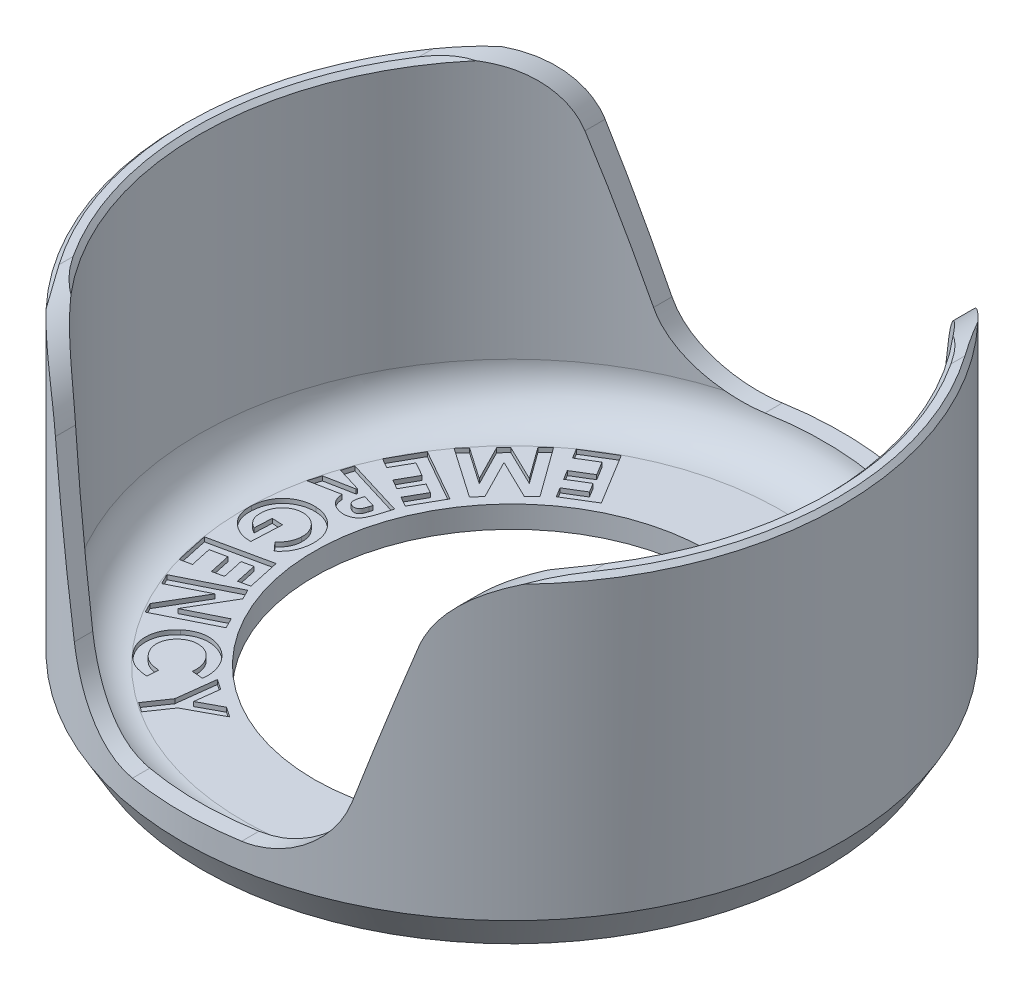
SolidWorks part; units mm, degrees
ref_plane "Front Plane" through (0, 0, 0) normal (0, 0, 1) x (1, 0, 0)
ref_plane "Top Plane" through (0, 0, 0) normal (0, 1, 0) x (1, 0, 0)
ref_plane "Right Plane" through (0, 0, 0) normal (1, 0, 0) x (0, 0, -1)
sketch "Sketch1" plane through (0, 0, 0) normal (0, 1, 0) x (1, 0, 0)
  circle A0 centre (0, 0) radius 37.5
  circle A1 centre (0, 0) radius 22.5
  dimension "D1" = 75
  dimension "D2" = 45
extrude "Boss-Extrude1" add sketch "Sketch1" along normal blind 2.5
sketch "Sketch2" plane through (0, 2.5, 0) normal (0, 1, 0) x (1, 0, 0)
  circle A0 centre (0, 0) radius 35.6108
  circle A1 centre (0, 0) radius 37.5
extrude "Boss-Extrude2" add sketch "Sketch2" along normal blind 35
fillet "Fillet1" radius 5 1 edges at (0, 2.5, 35.6108)
chamfer "Chamfer1" distance 0.5 angle 45 2 edges at (0, 37.5, 37.5) (0, 37.5, 35.6108)
sketch "Sketch3" plane through (0, 0, 0) normal (0, 0, 1) x (1, 0, 0)
  line L8 (36.1108, 37.5) -> (-36.1108, 37.5) construction
  line L15 (22.8069, 37.5) -> (13.6775, 6.7652)
  line L16 (-13.6775, 6.7652) -> (-22.8069, 37.5)
  line L17 (-22.8069, 37.5) -> (22.8069, 37.5)
  line L18 (-13.6775, 6.7652) -> (13.6775, 6.7652)
  point P4 (0, 27.5)
  point P6 (0, 0)
  point P10 (0, 37.5)
  point P12 (0, 27)
  point P15 (0, 27.5)
extrude "Cut-Extrude2" cut sketch "Sketch3" against normal mid plane 109
fillet "Fillet2" radius 10 8 edges at (-22.8069, 37.5, -28.566) (-22.8069, 37.5, 28.566) (22.8069, 37.5, 28.566) (22.8069, 37.5, -28.566) (-13.6775, 6.7652, -33.8686) (13.6775, 6.7652, -33.8686) (13.6775, 6.7652, 33.8686) (-13.6775, 6.7652, 33.8686)
sketch "Sketch4" plane through (0, 2.5, 0) normal (0, 1, 0) x (1, 0, 0)
  text T0 "<b>                             EMERGENCY    </b>" font "Century Gothic" height in points 26
  text T1 "<b>        STOP</b>" font "Century Gothic" height in points 26
extrude "Cut-Extrude3" cut sketch "Sketch4" against normal blind 0.5
scale "Scale1" scale about centroid uniform scaling yes scale factor 0.9
chamfer "Chamfer2" distance 2 angle 60 1 edges at (0.0063, 1.1049, 33.7511) first distance on face at (0.0063, 1.1049, 33.7511)
